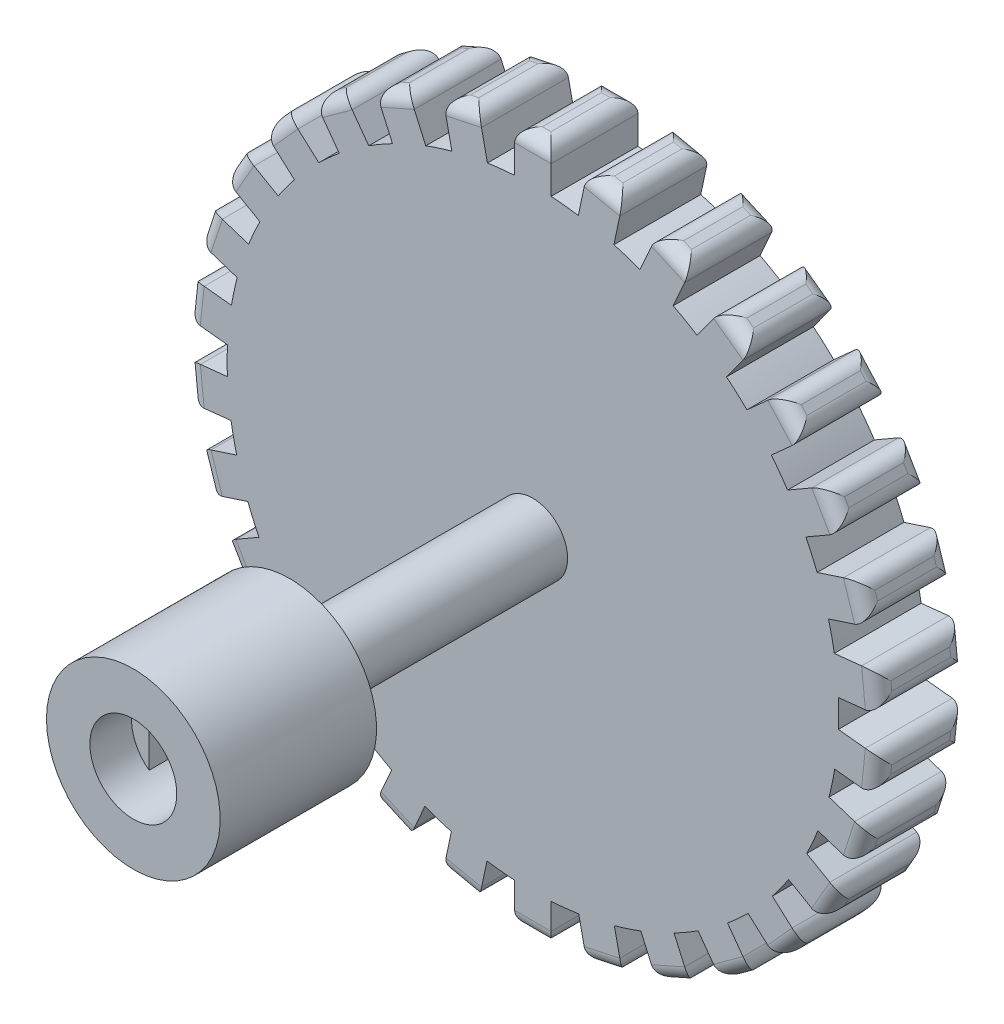
SolidWorks part; units mm, degrees
ref_plane "Front Plane" through (0, 0, 0) normal (0, 0, 1) x (1, 0, 0)
ref_plane "Top Plane" through (0, 0, 0) normal (0, 1, 0) x (1, 0, 0)
ref_plane "Right Plane" through (0, 0, 0) normal (1, 0, 0) x (0, 0, -1)
sketch "Sketch1" plane through (0, 0, 0) normal (0, 0, 1) x (1, 0, 0)
  circle A0 centre (0, 0) radius 88
extrude "Boss-Extrude3" add sketch "Sketch1" along normal blind 25
sketch "Sketch4" plane through (0, 0, 25) normal (0, 0, 1) x (1, 0, 0)
  line L0 (0, 88) -> (0, 100) construction
  line L1 (5.236, 100) -> (-5.236, 100)
  line L2 (-5.236, 100) -> (-5.236, 86.6488)
  line L3 (-5.236, 86.6488) -> (5.236, 86.6488)
  line L4 (5.236, 86.6488) -> (5.236, 100)
  circle A0 centre (0, 0) radius 88 construction
  point P9 (0, 100)
extrude "Boss-Extrude4" add sketch "Sketch4" against normal blind 25
fillet "Fillet2" radius 4 4 edges at (-5.236, 100, 12.5) (0, 100, 25) (0, 100, 0) (5.236, 100, 12.5)
pattern_circular "CirPattern1" count 30 over 360 about axis through (0, 0.3177, 0) along (0, 0, 1) of "Fillet2", "Boss-Extrude4"
ref_plane "Plane1" through (-5.236, 96, 25) normal (-1, 0, 0) x (0, 0, 1)
sketch "Sketch6" plane through (0, 0, 25) normal (0, 0, 1) x (1, 0, 0)
  circle A0 centre (0, 0) radius 10
extrude "Boss-Extrude5" add sketch "Sketch6" along normal blind 60
sketch "Sketch7" plane through (0, 0, 0) normal (0, 0, -1) x (-1, 0, 0)
  circle A0 centre (0, 0) radius 10
extrude "Boss-Extrude6" add sketch "Sketch7" along normal blind 10
sketch "Sketch8" plane through (0, 0, 85) normal (0, 0, 1) x (1, 0, 0)
  circle A0 centre (0, 0) radius 10
extrude "Boss-Extrude7" add sketch "Sketch8" along normal blind 10
sketch "Sketch9" plane through (0, 0, 95) normal (0, 0, 1) x (1, 0, 0)
  circle A0 centre (0, 0) radius 10
extrude "Boss-Extrude8" add sketch "Sketch9" along normal blind 25
sketch "Sketch10" plane through (0, 0, 120) normal (0, 0, 1) x (1, 0, 0)
  circle A0 centre (0, 0) radius 10
extrude "Boss-Extrude9" add sketch "Sketch10" along normal blind 42.5
sketch "Sketch12" plane through (0, 0, 162.5) normal (0, 0, 1) x (1, 0, 0)
  circle A0 centre (0, 0) radius 12.5
extrude "Cut-Extrude1" cut sketch "Sketch12" against normal blind 12
sketch "Sketch13" plane through (0, 0, 150.5) normal (0, 0, 1) x (1, 0, 0)
  circle A0 centre (0, 0) radius 10
extrude "Cut-Extrude2" cut sketch "Sketch13" against normal blind 55.5
sketch "Sketch14" plane through (0, 0, 95) normal (0, 0, 1) x (1, 0, 0)
  circle A0 centre (0, 0) radius 25
extrude "Boss-Extrude10" add sketch "Sketch14" along normal blind 45
sketch "Sketch15" plane through (0, 0, 140) normal (0, 0, 1) x (1, 0, 0)
  circle A0 centre (0, 0) radius 12.5
extrude "Cut-Extrude3" cut sketch "Sketch15" against normal blind 12
sketch "Sketch16" plane through (0, 0, 128) normal (0, 0, 1) x (1, 0, 0)
  line L2 (7.45, -10.0373) -> (7.45, 10.0373)
  line L4 (-7.45, -10.0373) -> (-7.45, 10.0373)
  line L5 (3.5287, -11.9916) -> (-3.5287, 11.9916) construction
  line L6 (3.5287, 11.9916) -> (-3.5287, -11.9916) construction
  arc A0 (7.45, 10.0373) -> (-7.45, 10.0373) centre (0, 0) ccw
  arc A1 (-7.45, -10.0373) -> (7.45, -10.0373) centre (0, 0) ccw
  point P0 (0, 0)
extrude "Cut-Extrude4" cut sketch "Sketch16" against normal blind 30.5
